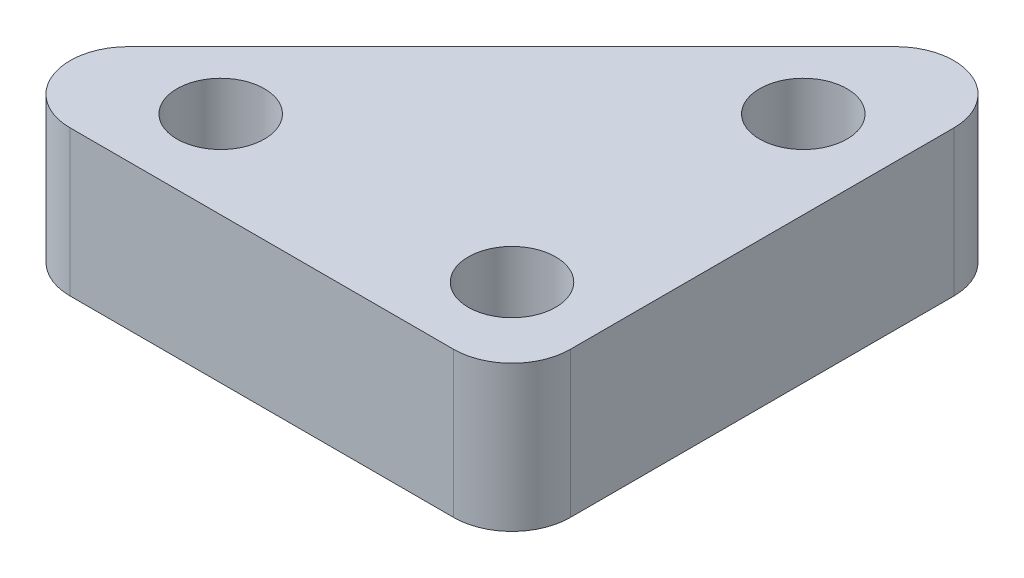
SolidWorks part; units mm, degrees
ref_plane "前视" through (0, 0, 0) normal (0, 0, 1) x (1, 0, 0)
ref_plane "上视" through (0, 0, 0) normal (0, 1, 0) x (1, 0, 0)
ref_plane "右视" through (0, 0, 0) normal (1, 0, 0) x (0, 0, -1)
sketch "Sketch1" plane through (0, 0, 0) normal (0, 1, 0) x (1, 0, 0)
  line L0 (-1.0435, 6.5198) -> (-1.0435, -13.4802)
  line L1 (-1.0435, -13.4802) -> (-21.0435, -13.4802)
  line L2 (-21.0435, -13.4802) -> (-1.0435, 6.5198)
  dimension "D1" = 20
  dimension "D2" = 20
extrude "Boss-Extrude1" add sketch "Sketch1" along normal blind 5
fillet "Fillet1" radius 2 3 edges at (-1.0435, 2.5, 13.4802) (-21.0435, 2.5, 13.4802) (-1.0435, 2.5, -6.5198)
sketch "Sketch2" plane through (0, 5, 0) normal (0, 1, 0) x (1, 0, 0)
  line L0 (-1.0435, -11.4802) -> (-1.0435, 1.6914) construction
  line L1 (-16.2151, -13.4802) -> (-3.0435, -13.4802) construction
  circle A0 centre (-4.0435, -0.4802) radius 1.5
  circle A1 centre (-4.0435, -10.4802) radius 1.5
  circle A2 centre (-14.0435, -10.4802) radius 1.5
  point P6 (0, 0)
  point P7 (0, 0)
  point P8 (0, 0)
  dimension "D1" = 10
  dimension "D2" = 10
  dimension "D3" = 3
  dimension "D4" = 3
extrude "Cut-Extrude1" cut sketch "Sketch2" against normal through all
